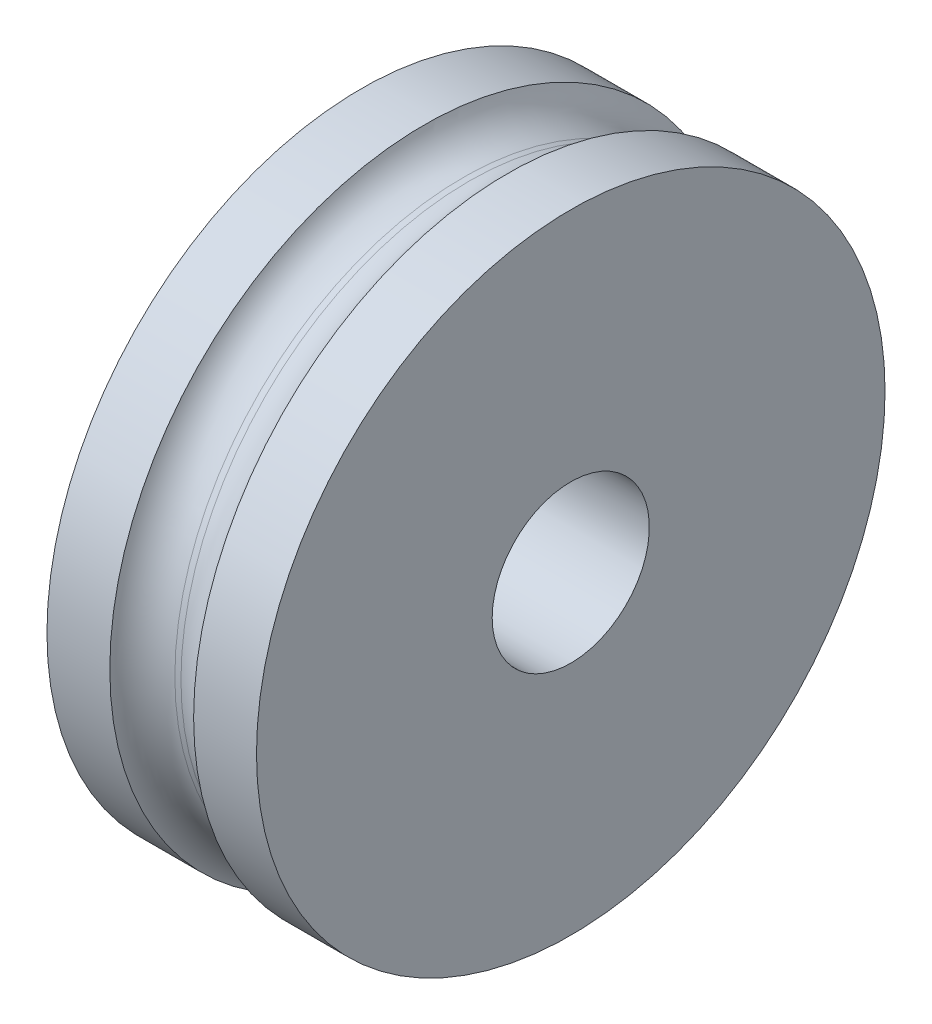
SolidWorks part; units mm, degrees
material "6061-T6 (SS)"
ref_plane "Front Plane" through (0, 0, 0) normal (0, 0, 1) x (1, 0, 0)
ref_plane "Top Plane" through (0, 0, 0) normal (0, 1, 0) x (1, 0, 0)
ref_plane "Right Plane" through (0, 0, 0) normal (1, 0, 0) x (0, 0, -1)
sketch "Sketch1" plane through (0, 0, 0) normal (0, 0, 1) x (1, 0, 0)
  line L0 (0, 0) -> (0, 4.7625) construction
  line L1 (6.35, 4.7625) -> (-6.35, 4.7625)
  line L2 (-6.35, 4.7625) -> (-6.35, 19.05)
  line L3 (6.35, 4.7625) -> (6.35, 19.05)
  line L4 (-6.35, 19.05) -> (-2.54, 19.05)
  line L5 (6.35, 19.05) -> (2.54, 19.05)
  line L6 (-2.54, 19.05) -> (-2.54, 17.4625)
  line L7 (2.54, 19.05) -> (2.54, 17.4625)
  line L8 (-2.54, 17.4625) -> (2.54, 17.4625)
  line L9 (-4.187, 0) -> (4.187, 0) construction
  point P6 (0, 4.7625)
  dimension "D1" = 12.7
  dimension "D2" = 3.81
  dimension "D3" = 19.05
  dimension "D4" = 4.7625
  dimension "D5" = 17.4625
revolve "Revolve1" add sketch "Sketch1" angle 360 about L9
fillet "Fillet1" radius 2.54 2 edges at (2.54, 0, 17.4625) (-2.54, 0, 17.4625)
